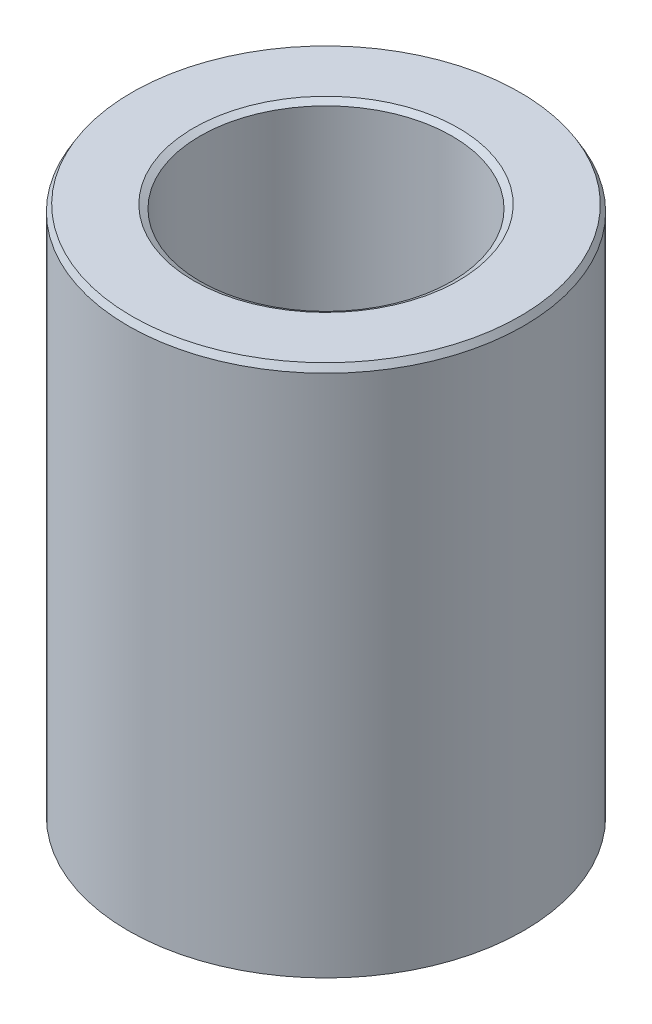
SolidWorks part; units mm, degrees
ref_plane "Front Plane" through (0, 0, 0) normal (0, 0, 1) x (1, 0, 0)
ref_plane "Top Plane" through (0, 0, 0) normal (0, 1, 0) x (1, 0, 0)
ref_plane "Right Plane" through (0, 0, 0) normal (1, 0, 0) x (0, 0, -1)
sketch "Sketch1" plane through (0, 0, 0) normal (0, 1, 0) x (1, 0, 0)
  circle A0 centre (0, 0) radius 57.5
  dimension "SLEEVE_OD" = 115
extrude "Boss-Extrude1" add sketch "Sketch1" along normal blind 155.2639
sketch "Sketch2" plane through (0, 0, 0) normal (0, 1, 0) x (1, 0, 0)
  circle A0 centre (0, 0) radius 36.6127
  dimension "BORE_D" = 73.2254
extrude "Cut-Extrude1" cut sketch "Sketch2" along normal through all
chamfer "Chamfer1" distance 1.8814 angle 30 4 edges at (0, 155.2639, 36.6127) (0, 0, 36.6127) (0, 0, 57.5) (0, 155.2639, 57.5) first distance on face at (0, 155.2639, 36.6127) first distance on face at (0, 0, 36.6127) first distance on face at (0, 155.2639, 57.5)
